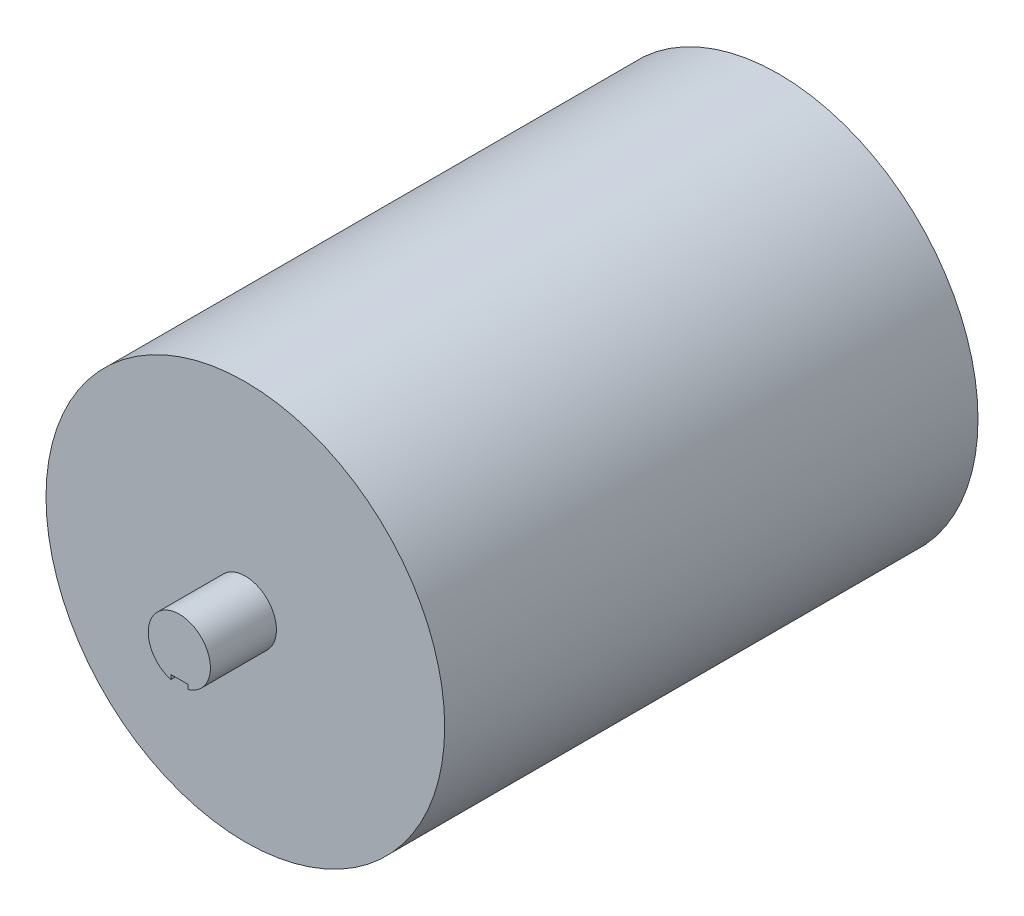
SolidWorks part; units mm, degrees
ref_plane "Front Plane" through (0, 0, 0) normal (0, 0, 1) x (1, 0, 0)
ref_plane "Top Plane" through (0, 0, 0) normal (0, 1, 0) x (1, 0, 0)
ref_plane "Right Plane" through (0, 0, 0) normal (1, 0, 0) x (0, 0, -1)
sketch "Sketch1" plane through (0, 0, 0) normal (0, 0, 1) x (1, 0, 0)
  circle A0 centre (0, 0) radius 38.5
  dimension "D1" = 77
extrude "Boss-Extrude1" add sketch "Sketch1" along normal blind 103
sketch "Sketch3" plane through (0, 0, 0) normal (1, 0, 0) x (0, 0, -1)
  line L0 (-103, 0) -> (-103, -6)
  line L1 (-103, 38.5) -> (-103, -38.5) construction
  line L5 (-115.7458, -6) -> (-115.7458, 0)
  line L6 (-115.7458, 0) -> (-103, 0)
  line L8 (-103, -6) -> (-118.42, -6) construction
  line L9 (-103, -6) -> (-115.7458, -6)
revolve "Revolve1" add sketch "Sketch3" angle 360 about L6
sketch "Sketch6" plane through (0, 0, 0) normal (0, 0, -1) x (-1, 0, 0)
  circle A0 centre (0, 0) radius 5
extrude "Boss-Extrude3" add sketch "Sketch6" along normal blind 12
sketch "Sketch7" plane through (0, 0, 115.7458) normal (0, 0, 1) x (1, 0, 0)
  line L0 (0, 6) -> (0, -4.9) construction
  line L1 (0, -4.9) -> (1.65, -4.9)
  line L2 (0, -4.9) -> (-1.65, -4.9)
  line L3 (-1.65, -4.9) -> (-1.65, -5.7687)
  line L4 (1.65, -4.9) -> (1.65, -5.7687)
  circle A0 centre (0, 0) radius 6 construction
  circle A1 centre (0, 0) radius 6 construction
  arc A2 (-1.65, -5.7687) -> (1.65, -5.7687) centre (0, 0) ccw
extrude "Cut-Extrude1" cut sketch "Sketch7" against normal blind 13 contours L1 L4 A2 L3 L2
